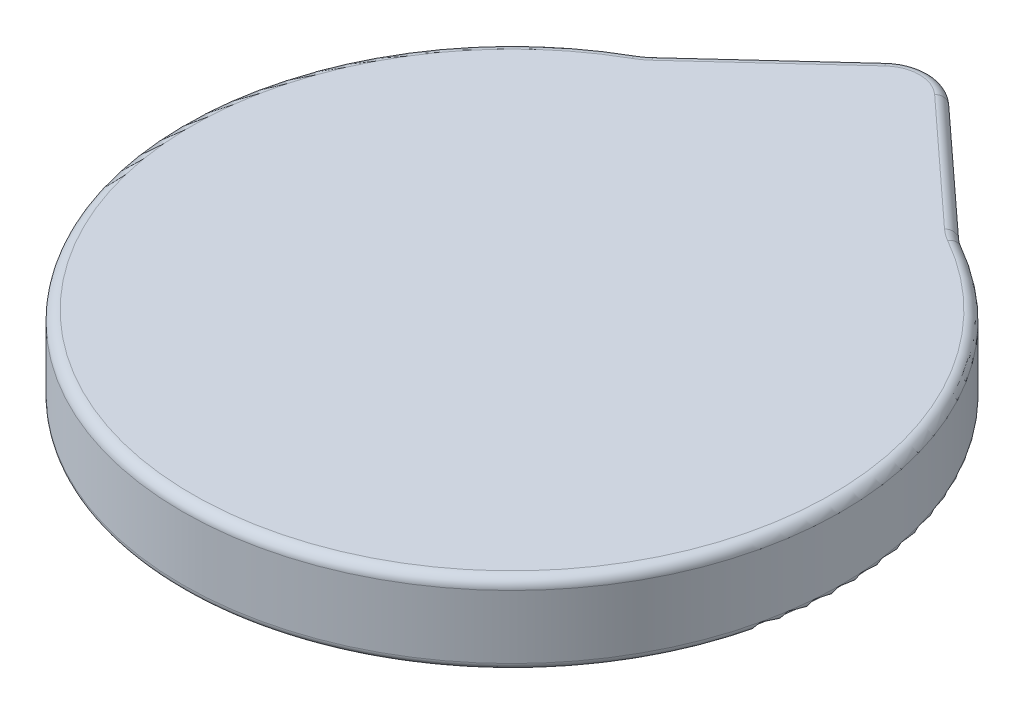
SolidWorks part; units mm, degrees
ref_plane "Front Plane" through (0, 0, 0) normal (0, 0, 1) x (1, 0, 0)
ref_plane "Top Plane" through (0, 0, 0) normal (0, 1, 0) x (1, 0, 0)
ref_plane "Right Plane" through (0, 0, 0) normal (1, 0, 0) x (0, 0, -1)
sketch "Sketch1" plane through (0, 0, 0) normal (0, 1, 0) x (1, 0, 0)
  line L0 (0, 0) -> (0, 125) construction
  line L1 (0, 125) -> (-45, 83.666)
  line L2 (0, 125) -> (45, 83.666)
  line L3 (45, 83.666) -> (-45, 83.666) construction
  circle A0 centre (0, 0) radius 95
  point P3 (0, 83.666)
  dimension "D1" = 190
  dimension "D2" = 125
  dimension "D3" = 90
sketch "Sketch2" plane through (0, 0, 0) normal (0, 1, 0) x (1, 0, 0)
  line L0 (0, 125) -> (-45, 83.666) construction
  line L1 (0, 125) -> (45, 83.666) construction
  line L2 (-6.7647, 118.7864) -> (-43.2424, 85.2804)
  line L3 (6.7647, 118.7864) -> (43.2424, 85.2804)
  line L4 (9.4706, 121.7323) -> (45.9483, 88.2263)
  line L5 (-9.4706, 121.7323) -> (-45.9483, 88.2263)
  arc A0 (-6.7647, 118.7864) -> (6.7647, 118.7864) centre (0, 111.4217) cw
  circle A1 centre (0, 0) radius 95
  arc A2 (-46.8985, 82.6168) -> (46.8985, 82.6168) centre (0, 0) ccw
  arc A3 (46.8985, 82.6168) -> (43.2424, 85.2804) centre (56.7718, 100.0098) cw
  arc A4 (-46.8985, 82.6168) -> (-43.2424, 85.2804) centre (-56.7718, 100.0098) ccw
  arc A5 (-48.8731, 86.0954) -> (48.8731, 86.0954) centre (0, 0) ccw
  arc A6 (48.8731, 86.0954) -> (45.9483, 88.2263) centre (56.7718, 100.0098) cw
  arc A7 (-9.4706, 121.7323) -> (9.4706, 121.7323) centre (0, 111.4217) cw
  arc A8 (-48.8731, 86.0954) -> (-45.9483, 88.2263) centre (-56.7718, 100.0098) ccw
  dimension "D2" = 10
  dimension "D3" = 20
  dimension "D1" = 0
  dimension "D4" = 4
extrude "Boss-Extrude1" add sketch "Sketch2" against normal blind 20
extrude "Boss-Extrude2" add sketch "Sketch2<2>" along normal blind 4 contours A5 A6 L4 A7 L5 A8
sketch "Sketch2<2>" plane through (0, 0, 0) normal (0, 1, 0) x (1, 0, 0) same geometry as "Sketch2"
fillet "Fillet1" radius 4 6 edges at (-44.9949, 0, -83.8449) (-25.0036, 0, -102.0334) (0, 0, -121.4217) (25.0036, 0, -102.0334) (44.9949, 0, -83.8449) (0, 0, 95)
fillet "Fillet2" radius 3 6 edges at (-47.3503, 4, -87.0779) (-27.7094, 4, -104.9793) (0, 4, -125.4217) (27.7094, 4, -104.9793) (47.3503, 4, -87.0779) (0, 4, 99)
fillet "Fillet3" radius 2 12 edges at (-44.9949, -20, -83.8449) (-25.0036, -20, -102.0334) (0, -20, -121.4217) (25.0036, -20, -102.0334) (44.9949, -20, -83.8449) (-47.3503, -20, -87.0779) (-27.7094, -20, -104.9793) (0, -20, -125.4217) (27.7094, -20, -104.9793) (47.3503, -20, -87.0779) (0, -20, 95) (0, -20, 99)
equation "\"D2@Sketch1\"=\"D1@Sketch1\"/2+3cm"
